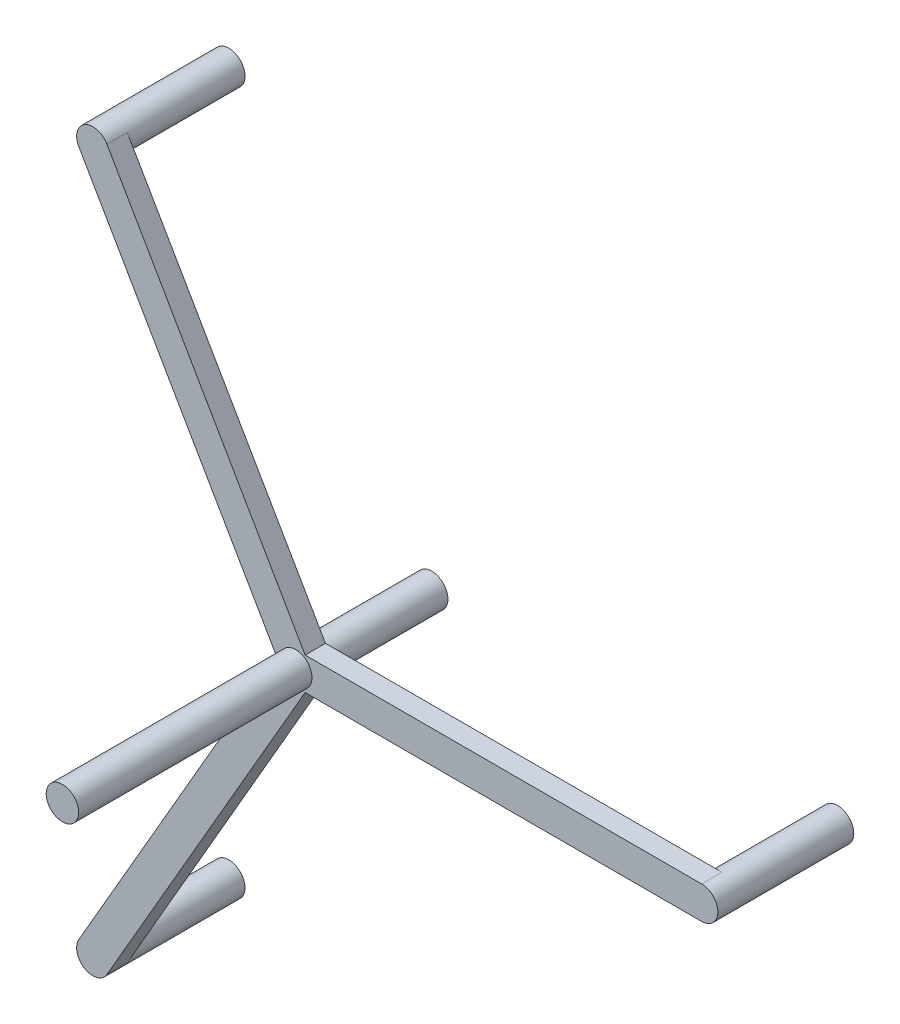
SolidWorks part; units mm, degrees
ref_plane "Front Plane" through (0, 0, 0) normal (0, 0, 1) x (1, 0, 0)
ref_plane "Top Plane" through (0, 0, 0) normal (0, 1, 0) x (1, 0, 0)
ref_plane "Right Plane" through (0, 0, 0) normal (1, 0, 0) x (0, 0, -1)
sketch "Sketch1" plane through (0, 0, 0) normal (0, 0, 1) x (1, 0, 0)
  line L0 (0, 0) -> (50, 0) construction
  line L1 (0, 2) -> (50, 2)
  line L2 (0, -2) -> (50, -2)
  circle A0 centre (0, 0) radius 2
  arc A1 (0, 2) -> (0, -2) centre (0, 0) ccw
  arc A2 (50, -2) -> (50, 2) centre (50, 0) ccw
  circle A3 centre (50, 0) radius 2
  point P3 (25, 0)
  dimension "D1" = 4
  dimension "D2" = 4
  dimension "D3" = 50
extrude "Boss-Extrude1" add sketch "Sketch1" along normal blind 1.25 and the other way blind 1.25 contours A0 L0 A3 L1 | L0 A0 L2 A3 region at (25, 1.0101, 0) region at (25, -1.0101, 0)
extrude "Boss-Extrude4" add sketch "Sketch1<5>" along normal blind 1.25 and the other way blind 15.5 contours A2 A3 | A0 region at (0, 0, 0) region at (50, 0, 0)
sketch "Sketch1<5>" plane through (0, 0, 0) normal (0, 0, 1) x (1, 0, 0) same geometry as "Sketch1"
extrude "Boss-Extrude5" add sketch "Sketch1<6>" along normal blind 30 contours A0
sketch "Sketch1<6>" plane through (0, 0, 0) normal (0, 0, 1) x (1, 0, 0) same geometry as "Sketch1"
pattern_circular "CirPattern1" count 3 over 360 about axis through (0, 0, 30) along (0, 0, 1) of "Boss-Extrude1", "Boss-Extrude4"
